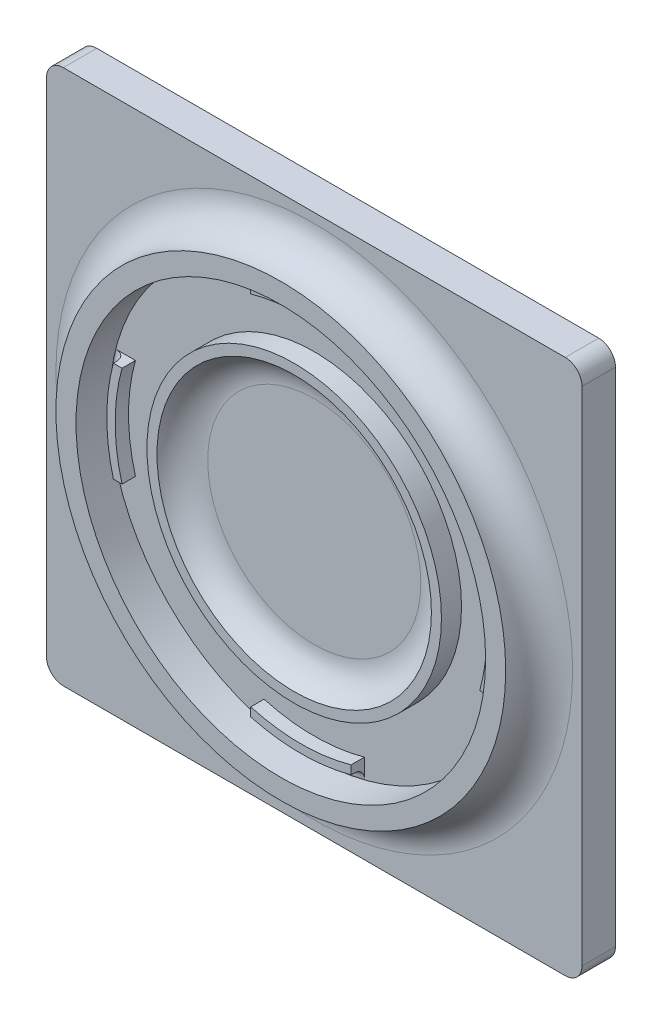
SolidWorks part; units mm, degrees
ref_plane "Front Plane" through (0, 0, 0) normal (0, 0, 1) x (1, 0, 0)
ref_plane "Top Plane" through (0, 0, 0) normal (0, 1, 0) x (1, 0, 0)
ref_plane "Right Plane" through (0, 0, 0) normal (1, 0, 0) x (0, 0, -1)
sketch "Sketch1" plane through (0, 0, 0) normal (0, 0, 1) x (1, 0, 0)
  line L1 (-40, 40) -> (40, 40)
  line L2 (-40, 40) -> (-40, -40)
  line L3 (-40, -40) -> (40, -40)
  line L4 (40, 40) -> (40, -40)
  line L5 (-40, 40) -> (40, -40) construction
  line L6 (-40, -40) -> (40, 40) construction
  point P0 (0, 0)
  dimension "D1" = 80
  dimension "D2" = 80
extrude "Boss-Extrude1" add sketch "Sketch1" along normal blind 5
fillet "Fillet1" radius 2.5 4 edges at (40, 40, 2.5) (-40, 40, 2.5) (40, -40, 2.5) (-40, -40, 2.5)
sketch "Sketch5" plane through (0, 0, 5) normal (0, 0, 1) x (1, 0, 0)
  line L5 (0, 29) -> (0, 27.75) construction
  line L6 (-7.5, 29) -> (7.5, 29)
  line L11 (-7.5, 29) -> (-7.5, -29)
  line L12 (-7.5, -29) -> (7.5, -29)
  line L16 (7.5, 29) -> (7.5, -29)
  line L17 (-7.5, 29) -> (7.5, -29) construction
  line L18 (-7.5, -29) -> (7.5, 29) construction
  line L19 (-29, 7.5) -> (29, 7.5)
  line L20 (-29, 7.5) -> (-29, -7.5)
  line L21 (-29, -7.5) -> (29, -7.5)
  line L22 (29, 7.5) -> (29, -7.5)
  line L23 (-29, 7.5) -> (29, -7.5) construction
  line L24 (-29, -7.5) -> (29, 7.5) construction
  line L26 (-2, 29.0722) -> (2, 29.0722)
  line L27 (-2, 29.0722) -> (-2, 27.6778)
  line L28 (-2, 27.6778) -> (2, 27.6778)
  line L29 (2, 29.0722) -> (2, 27.6778)
  line L30 (-2, 29.0722) -> (2, 27.6778) construction
  line L31 (-2, 27.6778) -> (2, 29.0722) construction
  circle A8 centre (0, 0) radius 27.75
  circle A9 centre (0, 0) radius 29
  point P14 (0, 28.375)
  dimension "D1" = 58
  dimension "D2" = 55.5
  dimension "D3" = 15
  dimension "D4" = 58
  dimension "D5" = 15
  dimension "D6" = 58
  dimension "D7" = 4
extrude "Boss-Extrude5" add sketch "Sketch5" along normal blind 2 contours L19 A9 L21 A8 | L27 A9 L11 A8 | L16 A9 L29 A8 | A9 L19 A8 L21 | L11 A9 L16 A8 region at (-4.7654, 27.9252, 5) region at (-28.0376, 0, 5) region at (4.7654, 27.9252, 5) region at (28.0376, 0, 5) region at (0, -28.0376, 5)
sketch "Sketch12" plane through (0, 0, 5) normal (0, 0, 1) x (1, 0, 0)
  circle A0 centre (0, 0) radius 30.6
  circle A1 centre (0, 0) radius 33.6
  dimension "D1" = 61.2
  dimension "D2" = 67.2
extrude "Boss-Extrude8" add sketch "Sketch12" along normal blind 5
sketch "Sketch13" plane through (0, 0, 5) normal (0, 0, 1) x (1, 0, 0)
  circle A0 centre (0, 0) radius 20.5
  circle A1 centre (0, 0) radius 22
  dimension "D1" = 44
  dimension "D2" = 41
extrude "Boss-Extrude9" add sketch "Sketch13" along normal blind 3
fillet "Fillet2" radius 1.5 5 edges at (29, 0, 5) (0, -29, 5) (-29, 0, 5) (4.7721, 28.6047, 5) (-4.7721, 28.6047, 5)
fillet "Fillet3" radius 5 2 edges at (33.6, 0, 5) (20.5, 0, 5)
